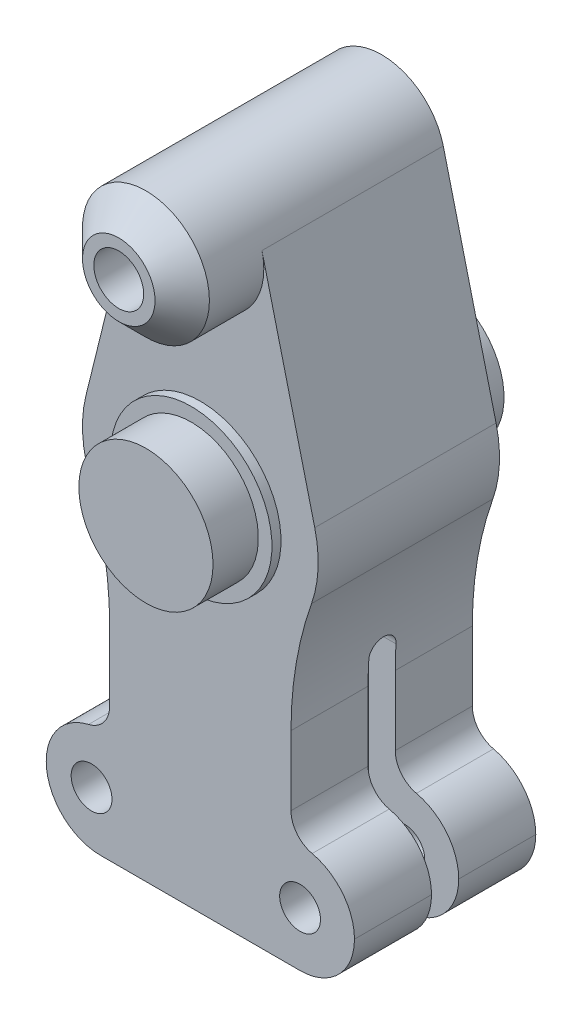
SolidWorks part; units mm, degrees
ref_plane "Спереди" through (0, 0, 0) normal (0, 0, 1) x (1, 0, 0)
ref_plane "Сверху" through (0, 0, 0) normal (0, 1, 0) x (1, 0, 0)
ref_plane "Справа" through (0, 0, 0) normal (1, 0, 0) x (0, 0, -1)
sketch "Эскиз1" plane through (0, 0, 0) normal (0, 0, 1) x (1, 0, 0)
  circle A0 centre (0, 0) radius 7.5 construction
  circle A1 centre (0, 0) radius 7.4
  dimension "D1" = 15
  dimension "measurement_tolerance" = 0.1
extrude "Бобышка-Вытянуть1" add sketch "Эскиз1" along normal blind 5
sketch "Эскиз2" plane through (0, 0, 0) normal (0, 0, -1) x (-1, 0, 0)
  circle A2 centre (0, 0) radius 8.9
  circle A3 centre (0, 0) radius 8.9
  dimension "D1" = 1.5
extrude "Бобышка-Вытянуть2" add sketch "Эскиз2" along normal blind 1
sketch "Эскиз3" plane through (0, 0, -1) normal (0, 0, -1) x (-1, 0, 0)
  circle A0 centre (0, 0) radius 13
  dimension "D3" = 26
extrude "Бобышка-Вытянуть3" add sketch "Эскиз3" along normal blind 20
sketch "Эскиз11" plane through (0, 0, 0) normal (0, 1, 0) x (1, 0, 0)
  line L1 (-10, 1) -> (10, 1)
  line L2 (0, 21) -> (0, 1) construction
  line L3 (13, 21) -> (-13, 21) construction
  line L4 (-8.9, 1) -> (8.9, 1) construction
  line L5 (-10, 1) -> (-10, 21)
  line L6 (-10, 21) -> (10, 21)
  line L7 (10, 1) -> (10, 21)
  line L8 (-10, 1) -> (10, 21) construction
  line L9 (-10, 21) -> (10, 1) construction
  point P0 (0, 11)
  dimension "D2" = 20
extrude "Бобышка-Вытянуть8" add sketch "Эскиз11" against normal blind 40
sketch "Эскиз4" plane through (0, 0, -1) normal (0, 0, -1) x (-1, 0, 0)
  line L0 (0, 0) -> (0, 25) construction
  line L1 (-6.7954, 26.68) -> (-12.62, 3.12)
  line L2 (-12.62, 3.12) -> (12.62, 3.12)
  line L4 (12.62, 3.12) -> (6.7954, 26.68)
  arc A0 (6.7954, 26.68) -> (-6.7954, 26.68) centre (0, 25) ccw
  circle A1 centre (0, 0) radius 13 construction
  dimension "D1" = 14
  dimension "D2" = 25
extrude "Бобышка-Вытянуть4" add sketch "Эскиз4" along normal up to surface (20 mm away) up to face at (0, -18.8267, -21)
sketch "Эскиз5" plane through (0, 0, -1) normal (0, 0, 1) x (1, 0, 0)
  circle A0 centre (0, 25) radius 7
  arc A1 (6.7954, 26.68) -> (-6.7954, 26.68) centre (0, 25) ccw construction
  dimension "D1" = 14
extrude "Бобышка-Вытянуть5" add sketch "Эскиз5" along normal blind 9
hole_wizard "Цековка для винта с внутренним шестигранником M51" positions "Эскиз7" profile "Эскиз6" counterbore size "M5" standard "Ansi Metric" end condition through all
sketch "Эскиз7" plane through (0.4817, 0.6241, -21) normal (0, 0, -1) x (-1, 0, 0)
  circle A0 centre (0.4817, 24.3759) radius 7 construction
  point P1 (0.4817, 24.3759)
sketch "Эскиз6" plane through (0, 25, -21) normal (1, 0, 0) x (0, 1, 0)
  line L0 (0, 0) -> (0, 29)
  line L1 (0, 29) -> (2.75, 29)
  line L3 (2.75, 29) -> (2.75, 14)
  line L4 (2.75, 14) -> (5.25, 14)
  line L5 (5.25, 14) -> (5.25, 0)
  line L7 (5.25, 0) -> (0, 0)
  line L11 (0, -6.35) -> (0, 107.95) construction
  dimension "Диаметр сквозного отверстия" = 5.5
  dimension "Глубина сквозного отверстия" = 29
  dimension "Диаметр цековки" = 10.5
chamfer "Фаска1" distance 3 angle 45 1 edges at (7, 25, 8)
fillet "Скругление20" radius 40 2 edges at (-10, -8.3066, -11) (10, -8.3066, -11)
sketch "Эскиз8" plane through (0, 0, -21) normal (0, 0, -1) x (-1, 0, 0)
  circle A1 centre (0, 0) radius 9
  circle A2 centre (0, 0) radius 7.5 construction
  dimension "D1" = 15
  dimension "D2" = 1.5
extrude "Бобышка-Вытянуть6" add sketch "Эскиз8" along normal blind 1
sketch "Эскиз9" plane through (0, 0, -22) normal (0, 0, -1) x (-1, 0, 0)
  circle A2 centre (0, 0) radius 7.5 construction
  circle A3 centre (0, 0) radius 7.5
  circle A4 centre (0, 0) radius 7.6 construction
  dimension "measurement_tolerance" = 0.1
extrude "Бобышка-Вытянуть7" add sketch "Эскиз9" along normal blind 5
sketch "Эскиз10" plane through (0, 0, 5) normal (0, 0, 1) x (1, 0, 0)
  circle A0 centre (0, 0) radius 3.25
  dimension "D1" = 6.5
extrude "Вырез-Вытянуть1" [suppressed] cut sketch "Эскиз10" against normal through all
sketch "Эскиз13" plane through (0, -40, 0) normal (0, -1, 0) x (-1, 0, 0)
  line L0 (10, 11) -> (-10, 11) construction
  line L1 (-10, 1) -> (-10, 21) construction
  line L2 (-17, 1) -> (17, 1)
  line L3 (-17, 1) -> (-17, 21)
  line L4 (-17, 21) -> (17, 21)
  line L5 (17, 1) -> (17, 21)
  line L6 (-17, 1) -> (17, 21) construction
  line L7 (-17, 21) -> (17, 1) construction
  line L8 (10, 21) -> (10, 1) construction
  point P0 (0, 11)
  dimension "D1" = 20
  dimension "D2" = 34
extrude "Бобышка-Вытянуть9" add sketch "Эскиз13" against normal blind 12
sketch "Эскиз14" plane through (0, -40, 0) normal (0, -1, 0) x (-1, 0, 0)
  line L0 (0, 1) -> (0, 11) construction
  line L1 (-17, 1) -> (17, 1) construction
  line L2 (0, 11) -> (17, 11) construction
  line L3 (17, 1) -> (17, 21) construction
  circle A0 centre (0, 11) radius 7.2
  dimension "D1" = 14.4
extrude "Вырез-Вытянуть3" cut sketch "Эскиз14" against normal blind 45
sketch "Эскиз15" plane through (0, -40, 0) normal (0, -1, 0) x (-1, 0, 0)
  line L0 (-17, 11) -> (17, 11) construction
  line L1 (-17, 12.5) -> (17, 12.5)
  line L2 (-17, 12.5) -> (-17, 9.5)
  line L3 (-17, 9.5) -> (17, 9.5)
  line L4 (17, 12.5) -> (17, 9.5)
  line L5 (-17, 21) -> (-17, 1) construction
  line L6 (17, 1) -> (17, 21) construction
  point P8 (0, 11)
  dimension "D1" = 3
extrude "Вырез-Вытянуть4" cut sketch "Эскиз15" against normal blind 25
sketch "Эскиз16" plane through (0, 0, 0) normal (1, 0, 0) x (0, 0, -1)
  line L0 (9.5, -15) -> (12.5, -15)
  line L1 (9.5, -15) -> (12.5, -15) construction
  arc A0 (12.5, -15) -> (9.5, -15) centre (11, -15) ccw
extrude "Вырез-Вытянуть5" cut sketch "Эскиз16" against normal through all and the other way through all
fillet "Скругление12" [suppressed] radius 3
fillet "Скругление14" radius 1 2 edges at (0, -40, -3.8) (0, -40, -18.2)
sketch "Эскиз17" plane through (0, 0, -21) normal (0, 0, -1) x (-1, 0, 0)
  line L0 (0, 25) -> (0, 15) construction
  line L1 (5.25, 25) -> (5.25, 15)
  line L2 (-5.25, 25) -> (-5.25, 15)
  circle A1 centre (0, 25) radius 5.25 construction
  arc A2 (5.25, 25) -> (-5.25, 25) centre (0, 25) ccw
  arc A3 (-5.25, 15) -> (5.25, 15) centre (0, 15) ccw
  point P5 (0, 20)
  dimension "D1" = 10
extrude "Вырез-Вытянуть6" cut sketch "Эскиз17" against normal offset from surface (14 mm away) 15 up to face at (4, 25, 8)
ref_plane "Плоскость1" through (0, 15, 0) normal (0, -1, 0) x (-1, 0, 0)
sketch "Эскиз18" plane through (0, 15, 0) normal (0, -1, 0) x (-1, 0, 0)
  line L0 (-5.25, 7) -> (5.25, 7)
  line L1 (5.25, 7) -> (5.25, 15.9272)
  line L2 (-5.25, 7) -> (-5.25, 15.9272)
  arc A0 (-5.25, 15.9272) -> (5.25, 15.9272) centre (0, 11) cw
  arc A2 (-7.042, 12.5) -> (7.042, 12.5) centre (0, 11) ccw construction
extrude "Вырез-Вытянуть7" cut sketch "Эскиз18" along normal through all
sketch "Эскиз19" plane through (0, 0, -27) normal (0, 0, -1) x (-1, 0, 0)
  line L1 (-2.7, -5.2) -> (2.7, -5.2)
  line L2 (-2.7, -5.2) -> (-2.7, 5.2)
  line L3 (-2.7, 5.2) -> (2.7, 5.2)
  line L4 (2.7, -5.2) -> (2.7, 5.2)
  line L5 (-2.7, -5.2) -> (2.7, 5.2) construction
  line L6 (-2.7, 5.2) -> (2.7, -5.2) construction
  point P0 (0, 0)
  dimension "D1" = 5.4
  dimension "D2" = 10.4
extrude "Вырез-Вытянуть8" cut sketch "Эскиз19" against normal blind 5
fillet "Скругление15" radius 1 3 edges at (5.25, 15, -7) (0, 30.25, -7) (-5.25, 15, -7)
fillet "Скругление18" radius 0.4 4 edges at (2.7, 5.2, -24.5) (-2.7, 5.2, -24.5) (2.7, -5.2, -24.5) (-2.7, -5.2, -24.5)
hole_wizard "Отверстие с зазором M41" positions "Эскиз21" profile "Эскиз20" hole size "M4" standard "Ansi Metric" end condition through all
sketch "Эскиз21" plane through (0, 0, -1) normal (0, 0, 1) x (1, 0, 0)
  line L0 (17, -34) -> (-17, -34) construction
  line L1 (17, -28) -> (17, -40) construction
  line L2 (-17, -28) -> (-17, -40) construction
  point P0 (-12, -34)
  point P2 (11, -34)
  dimension "D1" = 6
  dimension "D2" = 5
sketch "Эскиз20" plane through (-12, -34, -1) normal (1, 0, 0) x (0, -1, 0)
  line L0 (0, 0) -> (0, 26)
  line L1 (0, 26) -> (2.25, 26)
  line L2 (2.25, 26) -> (2.25, 0)
  line L5 (2.25, 0) -> (0, 0)
  line L11 (0, -6.35) -> (0, 107.95) construction
  dimension "Диаметр сквозного отверстия" = 4.5
  dimension "Глубина сквозного отверстия" = 26
fillet "Скругление19" radius 6 8 edges at (17, -28, -16.75) (17, -28, -5.25) (17, -40, -5.25) (17, -40, -16.75) (-17, -40, -16.75) (-17, -28, -16.75) (-17, -28, -5.25) (-17, -40, -5.25)
fillet "Скругление21" radius 3 4 edges at (10, -28, -16.75) (10, -28, -5.25) (-10, -28, -16.75) (-10, -28, -5.25)
